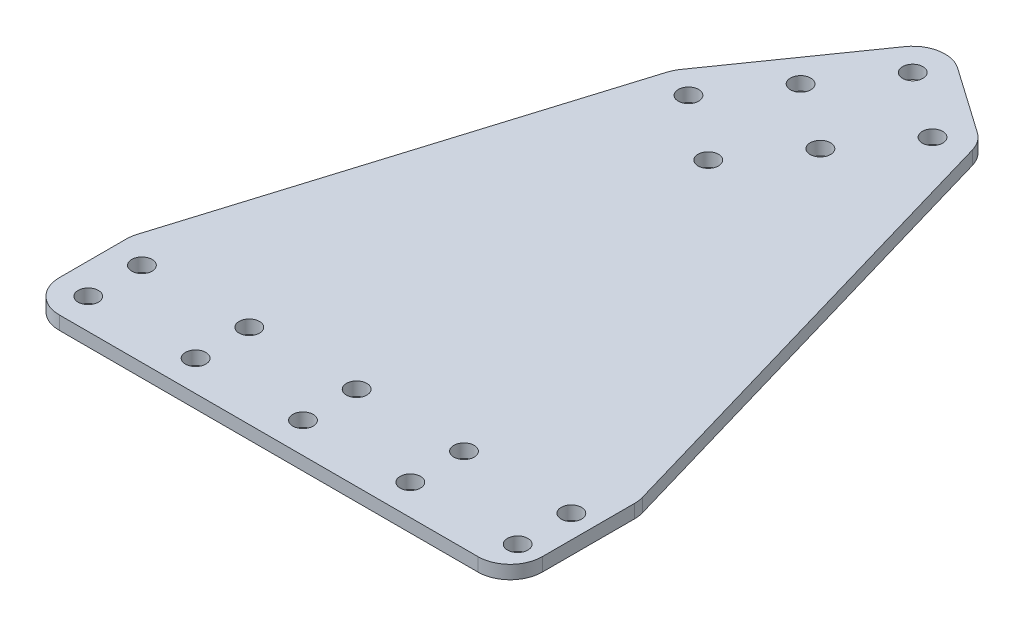
SolidWorks part; units mm, degrees
material "6061-T6 (SS)"
ref_plane "Front Plane" through (0, 0, 0) normal (0, 0, 1) x (1, 0, 0)
ref_plane "Top Plane" through (0, 0, 0) normal (0, 1, 0) x (1, 0, 0)
ref_plane "Right Plane" through (0, 0, 0) normal (1, 0, 0) x (0, 0, -1)
sketch "Sketch1" plane through (0, 0, 0) normal (0, 1, 0) x (1, 0, 0)
  line L5 (0, 0) -> (114.3, 0)
  line L6 (0, 0) -> (0, 181.61)
  line L7 (0, 181.61) -> (114.3, 181.61)
  line L8 (114.3, 0) -> (114.3, 181.61)
  dimension "D1" = 181.61
  dimension "D2" = 114.3
extrude "Boss-Extrude1" add sketch "Sketch1" along normal blind 3.175
sketch "Sketch2" plane through (0, 3.175, 0) normal (0, 1, 0) x (1, 0, 0)
  line L0 (0, 0) -> (114.3, 0) construction
  line L1 (0, 181.61) -> (0, 0) construction
  circle A0 centre (7.239, 7.239) radius 2.413
  circle A2 centre (7.239, 19.939) radius 2.413
  circle A3 centre (32.639, 19.939) radius 2.413
  circle A4 centre (58.039, 19.939) radius 2.413
  circle A5 centre (83.439, 19.939) radius 2.413
  circle A6 centre (108.839, 19.939) radius 2.413
  circle A7 centre (32.639, 7.239) radius 2.413
  circle A8 centre (58.039, 7.239) radius 2.413
  circle A9 centre (83.439, 7.239) radius 2.413
  circle A10 centre (108.839, 7.239) radius 2.413
  dimension "D1" = 4.826
  dimension "D2" = 7.239
  dimension "D3" = 7.239
  dimension "D4" = 2
  dimension "D5" = 5
extrude "Cut-Extrude1" cut sketch "Sketch2" against normal through all
sketch "Sketch3" plane through (0, 0, 0) normal (0, -1, 0) x (1, 0, 0)
  line L10 (37.07, -119.4115) -> (58.9233, -150.6212) construction
  line L11 (37.07, -119.4115) -> (52.6748, -108.4849) construction
  line L12 (58.9233, -150.6212) -> (74.5281, -139.6946) construction
  line L13 (52.6748, -108.4849) -> (74.5281, -139.6946) construction
  line L14 (0, -1.7463) -> (0, 1.7463) construction
  circle A14 centre (37.07, -119.4115) radius 2.413
  circle A15 centre (52.6748, -108.4849) radius 2.413
  circle A16 centre (74.5281, -139.6946) radius 2.413
  circle A17 centre (58.9233, -150.6212) radius 2.413
  circle A18 centre (47.9966, -135.0164) radius 2.413
  circle A19 centre (63.6015, -124.0897) radius 2.413
  point P14 (18.1822, -93.2878)
  point P15 (21.4236, -96.1495)
  point P16 (37.07, -117.377)
  dimension "D4" = 19.05
  dimension "D5" = 108.4849
  dimension "D2" = 4.826
  dimension "D1" = 35
  dimension "D6" = 52.6748
  dimension "D3" = 19.05
extrude "Cut-Extrude2" cut sketch "Sketch3" against normal through all
sketch "Sketch4" plane through (0, 0, 0) normal (0, -1, 0) x (1, 0, 0)
  line L0 (57.052, -161.2338) -> (30.1383, -122.7972)
  line L2 (114.3, -181.61) -> (0, -181.61)
  line L3 (0, -181.61) -> (0, -24.617)
  line L5 (114.3, -30.5457) -> (81.0932, -144.3999)
  line L6 (114.3, 0) -> (114.3, -181.61) construction
  line L7 (114.3, -30.5457) -> (114.3, -181.61)
  line L9 (37.07, -119.4115) -> (58.9233, -150.6212) construction
  line L10 (58.9233, -150.6212) -> (74.5281, -139.6946) construction
  line L11 (57.052, -161.2338) -> (81.0932, -144.3999)
  line L12 (30.1383, -122.7972) -> (0, -24.617)
  line L13 (0, -1.7463) -> (0, 1.7463) construction
  circle A0 centre (74.5281, -139.6946) radius 2.413 construction
  circle A1 centre (58.9233, -150.6212) radius 2.413 construction
  circle A2 centre (37.07, -119.4115) radius 2.413 construction
  circle A3 centre (74.5281, -139.6946) radius 2.413 construction
  circle A4 centre (58.9233, -150.6212) radius 2.413 construction
  circle A5 centre (37.07, -119.4115) radius 2.413 construction
  circle A6 centre (108.839, -19.939) radius 2.413 construction
  circle A7 centre (7.239, -19.939) radius 2.413 construction
  circle A8 centre (108.839, -19.939) radius 2.413 construction
  circle A9 centre (7.239, -19.939) radius 2.413 construction
  dimension "D1" = 7.62
  dimension "D2" = 7.62
  dimension "D3" = 7.62
  dimension "D4" = 7.62
extrude "Cut-Extrude3" cut sketch "Sketch4" against normal through all
fillet "Fillet1" radius 7.62 7 edges at (114.3, 1.5875, -30.5457) (0, 1.5875, -24.617) (30.1383, 1.5875, -122.7972) (57.052, 1.5875, -161.2338) (81.0932, 1.5875, -144.3999) (0, 1.5875, 0) (114.3, 1.5875, 0)
